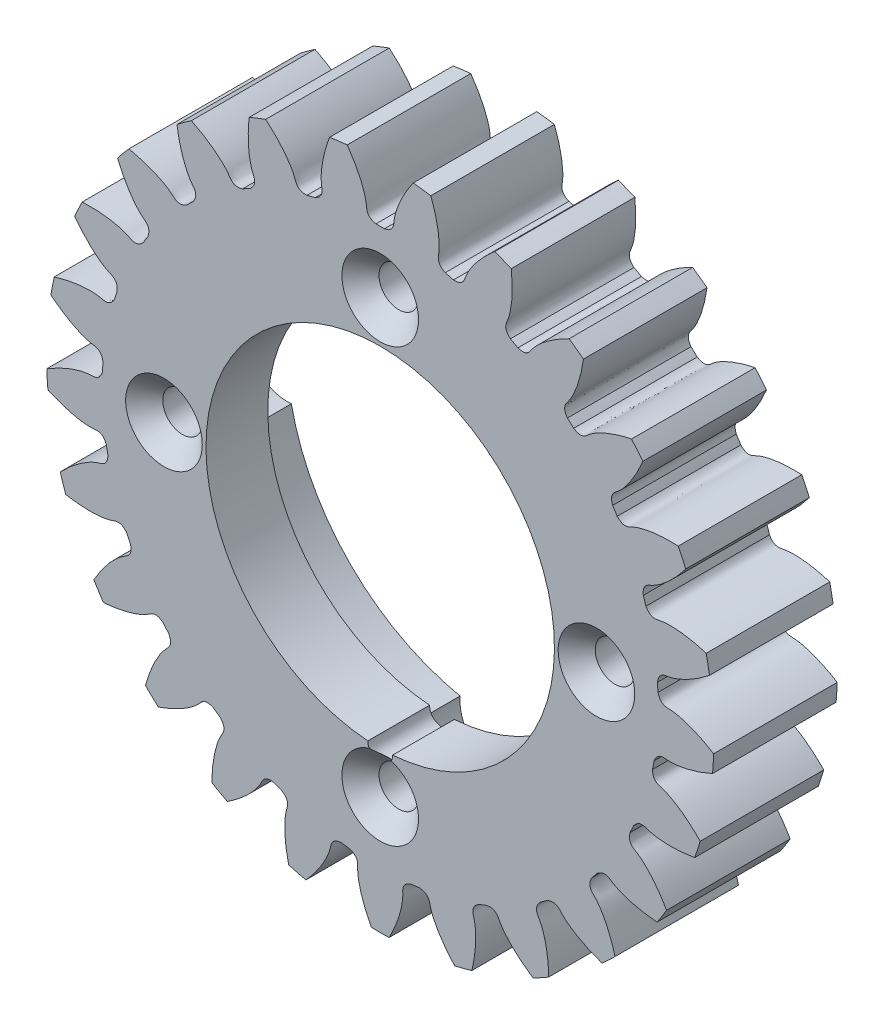
SolidWorks part; units mm, degrees
ref_plane "前视基准面" through (0, 0, 0) normal (0, 0, 1) x (1, 0, 0)
ref_plane "上视基准面" through (0, 0, 0) normal (0, 1, 0) x (1, 0, 0)
ref_plane "右视基准面" through (0, 0, 0) normal (1, 0, 0) x (0, 0, -1)
sketch "草图1" plane through (0, 0, 0) normal (0, 0, 1) x (1, 0, 0)
  circle A0 centre (0, 0) radius 27
extrude "凸台-拉伸1" add sketch "草图1" along normal blind 10
ref_axis "基准轴1" through (0, 0, 10) along (0, 0, -1)
sketch "草图2" plane through (0, 0, 0) normal (0, 0, 1) x (1, 0, 0)
  line L0 (0, 0) -> (0, 27) construction
  circle A0 centre (0, 0) radius 27 construction
  arc A1 (0.3441, 22.4974) -> (-0.3441, 22.4974) centre (0, 0) ccw
  arc A2 (6.4105, 30.6297) -> (-6.4105, 30.6297) centre (0, 0) ccw
  spline S0 degree 3 poles (0.3441, 22.4974) (1.1467, 22.6702) (1.071, 23.1545) (1.1484, 23.6361) (1.1592, 23.6962) (1.1732, 23.7653) (1.1905, 23.8433) (1.2116, 23.93) (1.2368, 24.0254) (1.2665, 24.1293) (1.301, 24.2416) (1.3407, 24.3621) (1.3859, 24.4906) (1.437, 24.6271) (1.4943, 24.7712) (1.5581, 24.9227) (1.6287, 25.0816) (1.7064, 25.2475) (1.7916, 25.4203) (1.8846, 25.5997) (1.9857, 25.7854) (2.095, 25.9773) (2.2131, 26.175) (2.34, 26.3782) (2.4761, 26.5868) (2.6216, 26.8004) (2.7768, 27.0186) (2.9419, 27.2413) (3.1172, 27.468) (3.303, 27.6986) (3.4993, 27.9325) (3.7064, 28.1696) (3.9246, 28.4094) (4.1539, 28.6517) (4.3947, 28.896) (4.647, 29.142) (4.9111, 29.3893) (5.187, 29.6376) (5.475, 29.8865) (5.8799, 30.2225) (6.1949, 30.4682) (6.4105, 30.6297) knots 0 0 0 0 0.130741 0.135745 0.141658 0.148481 0.156214 0.164857 0.174409 0.184871 0.196243 0.208524 0.221715 0.235816 0.250827 0.266748 0.283578 0.301318 0.319968 0.339527 0.359996 0.381375 0.403664 0.426862 0.450971 0.475988 0.501916 0.528753 0.556501 0.585157 0.614724 0.6452 0.676587 0.708882 0.742088 0.776203 0.811228 0.847163 0.884008 0.921762 1 1 1 1
  spline S1 degree 3 poles (-0.3441, 22.4974) (-1.1467, 22.6702) (-1.071, 23.1545) (-1.1484, 23.6361) (-1.1592, 23.6962) (-1.1732, 23.7653) (-1.1905, 23.8433) (-1.2116, 23.93) (-1.2368, 24.0254) (-1.2665, 24.1293) (-1.301, 24.2416) (-1.3407, 24.3621) (-1.3859, 24.4906) (-1.437, 24.6271) (-1.4943, 24.7712) (-1.5581, 24.9227) (-1.6287, 25.0816) (-1.7064, 25.2475) (-1.7916, 25.4203) (-1.8846, 25.5997) (-1.9857, 25.7854) (-2.095, 25.9773) (-2.2131, 26.175) (-2.34, 26.3782) (-2.4761, 26.5868) (-2.6216, 26.8004) (-2.7768, 27.0186) (-2.9419, 27.2413) (-3.1172, 27.468) (-3.303, 27.6986) (-3.4993, 27.9325) (-3.7064, 28.1696) (-3.9246, 28.4094) (-4.1539, 28.6517) (-4.3947, 28.896) (-4.647, 29.142) (-4.9111, 29.3893) (-5.187, 29.6376) (-5.475, 29.8865) (-5.8799, 30.2225) (-6.1949, 30.4682) (-6.4105, 30.6297) knots 0 0 0 0 0.130741 0.135745 0.141658 0.148481 0.156214 0.164857 0.174409 0.184871 0.196243 0.208524 0.221715 0.235816 0.250827 0.266748 0.283578 0.301318 0.319968 0.339527 0.359996 0.381375 0.403664 0.426862 0.450971 0.475988 0.501916 0.528753 0.556501 0.585157 0.614724 0.6452 0.676587 0.708882 0.742088 0.776203 0.811228 0.847163 0.884008 0.921762 1 1 1 1
extrude "切除-拉伸1" cut sketch "草图2" along normal through all
pattern_circular "阵列(圆周)1" count 25 every 14.4 about axis through (0, 0, 10) along (0, 0, -1) of "切除-拉伸1"
sketch "草图3" plane through (0, 0, 0) normal (0, 0, 1) x (1, 0, 0)
  circle A0 centre (0, 0) radius 25 construction
  dimension "Dn" = 50
sketch "草图4" plane through (0, 0, 10) normal (0, 0, 1) x (1, 0, 0)
  line L0 (0, -17.5) -> (0, -14.1) construction
  circle A0 centre (0, 0) radius 17.5 construction
  circle A1 centre (0, 17.5) radius 1.6
  circle A2 centre (-17.5, 0) radius 1.6
  circle A3 centre (17.5, 0) radius 1.6
  circle A4 centre (0, -17.5) radius 1.6
  arc A10 (0.9994, -14.0645) -> (-0.9994, -14.0645) centre (0, 0) ccw
  arc A11 (-0.9994, -14.0645) -> (0.9994, -14.0645) centre (0, -14.1) ccw
  dimension "D1" = 35
  dimension "D2" = 3.2
  dimension "D3" = 28.2
  dimension "D4" = 2
extrude "切除-拉伸2" cut sketch "草图4" against normal through all
sketch "草图5" plane through (0, 0, 0) normal (0, 0, -1) x (-1, 0, 0)
  arc A0 (3.5364, 17.19) -> (-3.5364, 17.19) centre (0, 17.5) ccw
  arc A1 (-17.19, 3.5364) -> (-17.19, -3.5364) centre (-17.5, 0) ccw
  arc A2 (-3.5364, -17.19) -> (3.5364, -17.19) centre (0, -17.5) ccw
  arc A3 (17.19, -3.5364) -> (17.19, 3.5364) centre (17.5, 0) ccw
  arc A4 (-17.19, -3.5364) -> (-3.5364, -17.19) centre (0, 0) ccw
  arc A5 (-3.5364, 17.19) -> (-17.19, 3.5364) centre (0, 0) ccw
  arc A6 (17.19, 3.5364) -> (3.5364, 17.19) centre (0, 0) ccw
  arc A7 (3.5364, -17.19) -> (17.19, -3.5364) centre (0, 0) ccw
  dimension "D1" = 7.1
  dimension "D2" = 17.55
extrude "切除-拉伸4" cut sketch "草图5" against normal blind 5
chamfer "倒角1" distance 1.5 angle 45 4 edges at (19.1, 0, 10) (1.6, -17.5, 10) (-15.9, 0, 10) (1.6, 17.5, 10)
